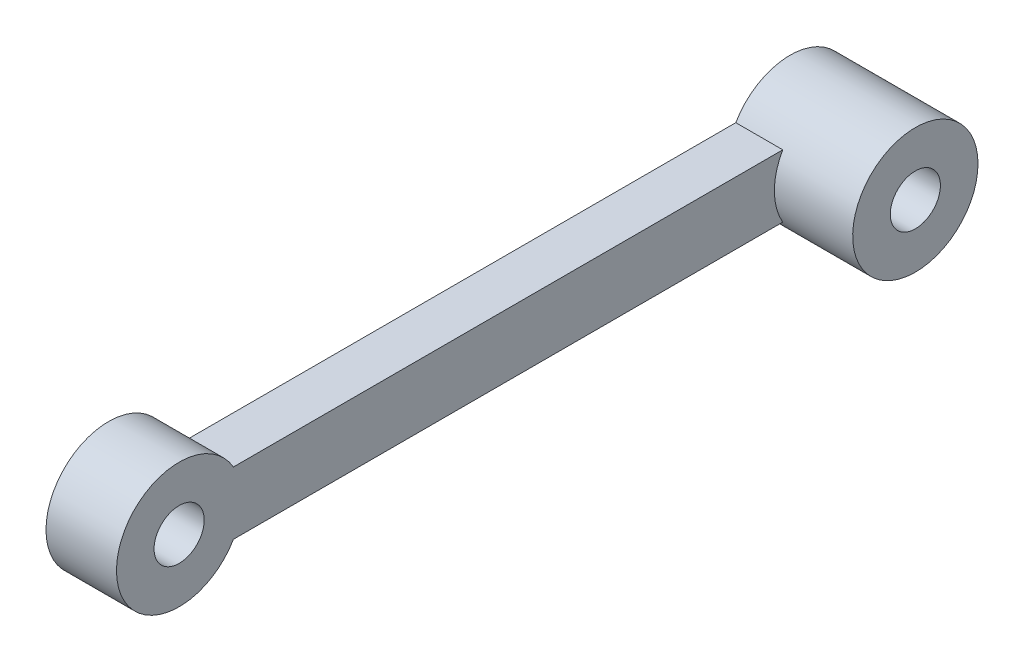
SolidWorks part; units mm, degrees
ref_plane "Front Plane" through (0, 0, 0) normal (0, 0, 1) x (1, 0, 0)
ref_plane "Top Plane" through (0, 0, 0) normal (0, 1, 0) x (1, 0, 0)
ref_plane "Right Plane" through (0, 0, 0) normal (1, 0, 0) x (0, 0, -1)
sketch "Sketch1" plane through (0, 0, 0) normal (1, 0, 0) x (0, 0, -1)
  line L2 (21, 2) -> (38.5359, 2)
  line L3 (21, 2) -> (3.4641, 2)
  line L5 (21, -2) -> (38.5359, -2)
  line L6 (21, -2) -> (3.4641, -2)
  arc A0 (38.5359, -2) -> (38.5359, 2) centre (42, 0) ccw
  arc A1 (3.4641, 2) -> (3.4641, -2) centre (0, 0) ccw
  circle A2 centre (0, 0) radius 1.6
  circle A3 centre (42, 0) radius 1.6
extrude "Boss-Extrude1" add sketch "Sketch1" along normal blind 3
sketch "Sketch2" plane through (0, 0, 0) normal (-1, 0, 0) x (0, 0, 1)
  circle A0 centre (0, 0) radius 1.6
  circle A1 centre (0, 0) radius 4
extrude "Boss-Extrude2" add sketch "Sketch2" along normal blind 1.5
sketch "Sketch3" plane through (3, 0, 0) normal (1, 0, 0) x (0, 0, -1)
  circle A0 centre (42, 0) radius 4
  circle A1 centre (42, 0) radius 1.6
extrude "Boss-Extrude3" add sketch "Sketch3" along normal blind 5
